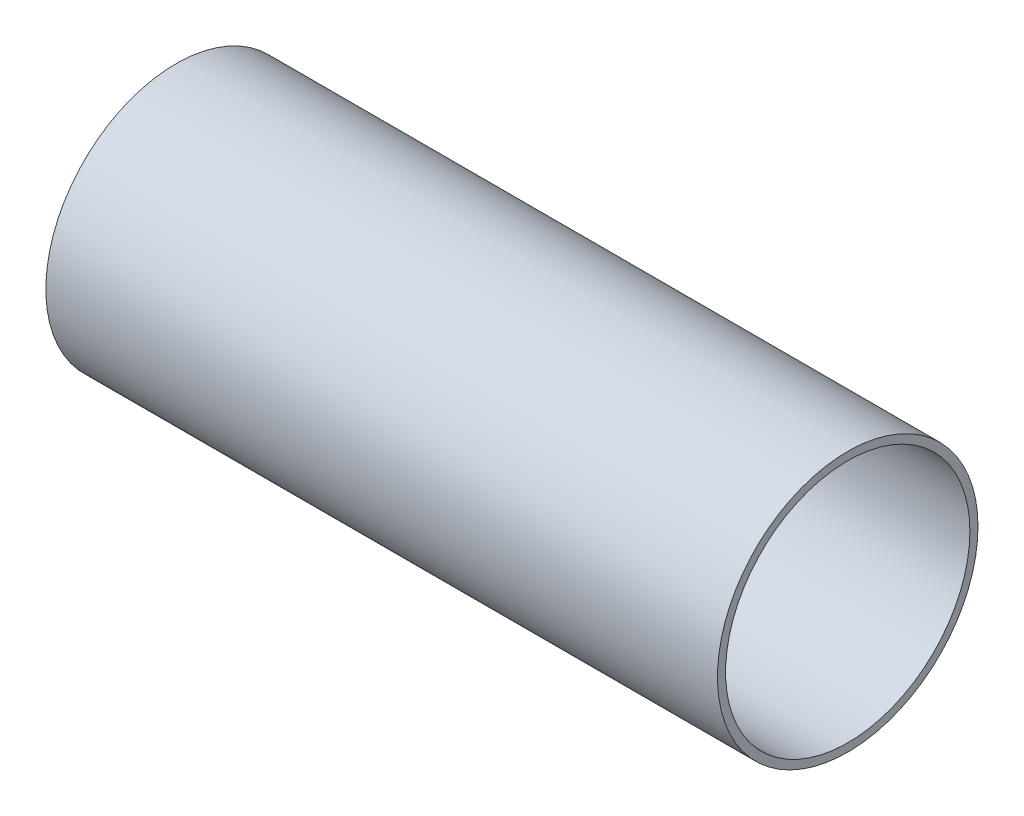
SolidWorks part; units mm, degrees
ref_plane "Front Plane" through (0, 0, 0) normal (0, 0, 1) x (1, 0, 0)
ref_plane "Top Plane" through (0, 0, 0) normal (0, 1, 0) x (1, 0, 0)
ref_plane "Right Plane" through (0, 0, 0) normal (1, 0, 0) x (0, 0, -1)
sketch "Sketch1" plane through (0, 0, 0) normal (1, 0, 0) x (0, 0, -1)
  circle A0 centre (0, 0) radius 14.2875
  circle A1 centre (0, 0) radius 13.3985
extrude "Boss-Extrude1" add sketch "Sketch1" along normal mid plane 73.66
